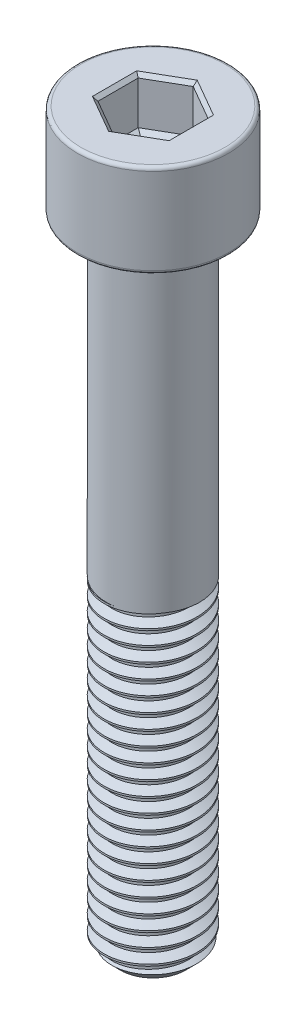
SolidWorks part; units mm, degrees
material "AISI Type A2 Tool Steel"
ref_plane "Front Plane" through (0, 0, 0) normal (0, 0, 1) x (1, 0, 0)
ref_plane "Top Plane" through (0, 0, 0) normal (0, 1, 0) x (1, 0, 0)
ref_plane "Right Plane" through (0, 0, 0) normal (1, 0, 0) x (0, 0, -1)
sketch "Sketch1" plane through (0, 0, 0) normal (0, 1, 0) x (1, 0, 0)
  circle A0 centre (0, 0) radius 4
  dimension "D1" = 8
extrude "Boss-Extrude1" add sketch "Sketch1" along normal blind 28
thread "Thread1" pitch 1.25 method cut profile "Thread Profile1" start angle 0, offset 2, length 0, pitch 1.25, diameter 8
ref_plane "Plane1" through (-4, 30, 0) normal (0, 0, 1) x (-1, 0, 0)
sketch "Thread Profile1" plane through (-4, 30, 0) normal (0, 0, 1) x (-1, 0, 0)
  line L0 (0, 0) -> (0, 1.25) construction
  line L11 (0, 0) -> (0, 1.0937)
  line L12 (0, 1.0937) -> (-0.6766, 0.7031)
  line L13 (-0.6766, 0.7031) -> (-0.6766, 0.3906)
  line L15 (-0.6766, 0.3906) -> (0, 0)
  line L17 (-0.6766, 0.5469) -> (0, 0.5469) construction
  point P2 (0, 0)
  dimension "Pitch" = 1.25
  dimension "Profile_Angle" = 60
  dimension "Profile_Land" = 0.3125
  dimension "Profile_Height" = 0.6766
sketch "Sketch2" plane through (0, 28, 0) normal (0, 1, 0) x (1, 0, 0)
  circle A0 centre (0, 0) radius 4
  dimension "D1" = 8
extrude "Boss-Extrude2" add sketch "Sketch2" along normal blind 27
sketch "Sketch5" plane through (0, 55, 0) normal (0, 1, 0) x (1, 0, 0)
  circle A0 centre (0, 0) radius 6.5
  dimension "D1" = 13
extrude "Boss-Extrude3" add sketch "Sketch5" along normal blind 8
sketch "Sketch6" plane through (0, 0, 0) normal (0, 0, 1) x (1, 0, 0)
  line L0 (0, 0) -> (0, 0.7245) construction
  line L1 (0, 0) -> (4.01, 0) construction
  line L2 (4.01, 0) -> (4.01, 1.2)
  line L3 (4.01, 1.2) -> (2.81, 0)
  line L4 (2.81, 0) -> (4.01, 0)
  dimension "D1" = 1.2
  dimension "D2" = 45
  dimension "D3" = 4.01
revolve "Cut-Revolve1" cut sketch "Sketch6" angle 360 about L0
fillet "Fillet1" radius 0.3 2 edges at (0, 55, 6.5) (0, 63, 6.5)
sketch "Sketch7" plane through (0, 63, 0) normal (0, 1, 0) x (1, 0, 0)
  line L1 (0, 3.4641) -> (-3, 1.7321)
  line L2 (-3, 1.7321) -> (-3, -1.7321)
  line L3 (-3, -1.7321) -> (0, -3.4641)
  line L4 (0, -3.4641) -> (3, -1.7321)
  line L5 (3, -1.7321) -> (3, 1.7321)
  line L6 (3, 1.7321) -> (0, 3.4641)
  circle A0 centre (0, 0) radius 3 construction
  dimension "D1" = 6
extrude "Cut-Extrude1" cut sketch "Sketch7" against normal blind 4
chamfer "Chamfer1" distance 0.3 angle 45 6 edges at (-3, 63, 0) (-1.5, 63, 2.5981) (1.5, 63, 2.5981) (3, 63, 0) (1.5, 63, -2.5981) (-1.5, 63, -2.5981)
sketch "Sketch8" plane through (0, 59, 0) normal (0, 1, 0) x (1, 0, 0)
  line L1 (0, 3.4641) -> (-3, 1.7321)
  line L2 (-3, 1.7321) -> (-3, -1.7321)
  line L3 (-3, -1.7321) -> (0, -3.4641)
  line L4 (0, -3.4641) -> (3, -1.7321)
  line L5 (3, -1.7321) -> (3, 1.7321)
  line L6 (3, 1.7321) -> (0, 3.4641)
  circle A0 centre (0, 0) radius 3 construction
extrude "Cut-Extrude2" cut sketch "Sketch8" against normal blind 0.4 draft 60
